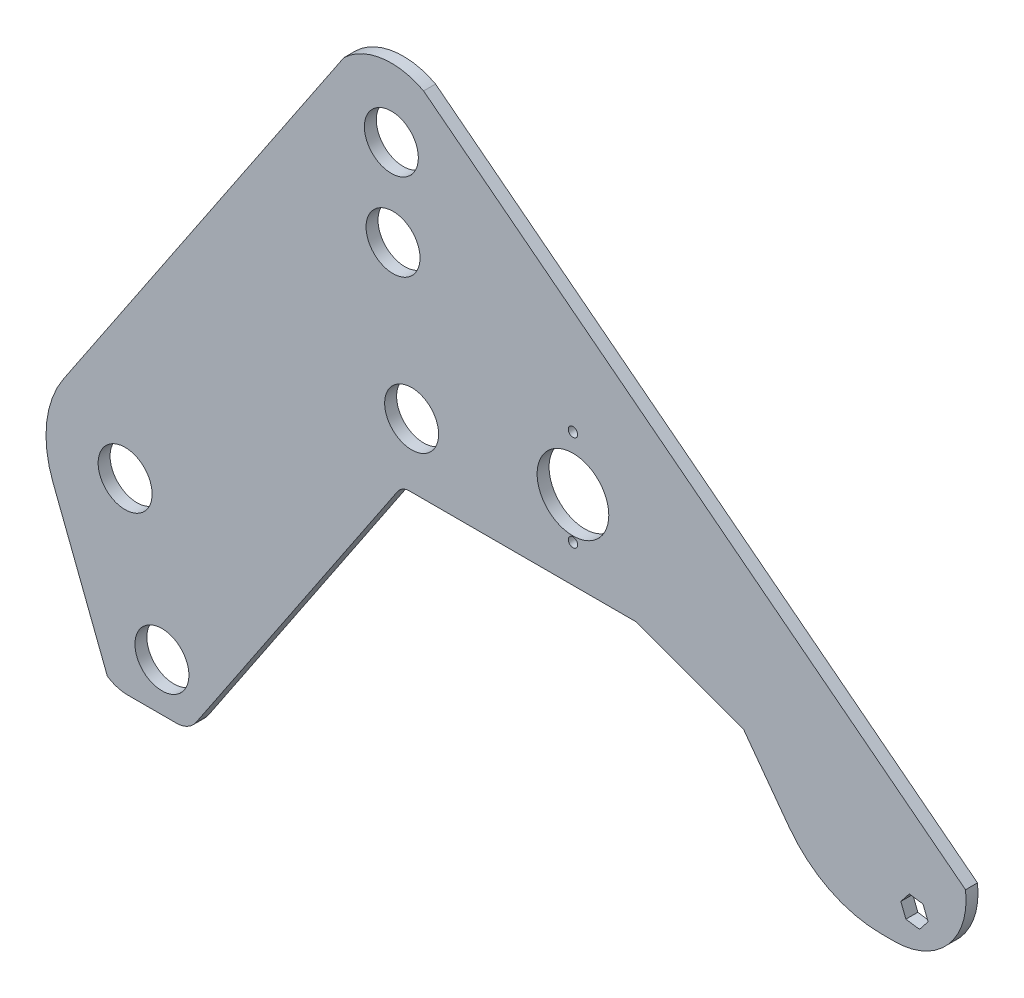
SolidWorks part; units mm, degrees
other "Markup1"
sketch "Sketch1" plane through (-441.7893, 331.8239, 6.35) normal (-0.0431, 0.0102, 0.999) x (0.9985, 0.0354, 0.0427)
sketch "Sketch2" plane through (-413.6701, 343.933, 6.35) normal (-0.0431, 0.0102, 0.999) x (0.9985, 0.0354, 0.0427)
ref_plane "Front Plane" through (0, 0, 0) normal (0, 0, 1) x (1, 0, 0)
ref_plane "Top Plane" through (0, 0, 0) normal (0, 1, 0) x (1, 0, 0)
ref_plane "Right Plane" through (0, 0, 0) normal (1, 0, 0) x (0, 0, -1)
sketch "Model" plane through (0, 0, 0) normal (0, 0, 1) x (1, 0, 0)
  line L1 (-220.9661, 94.4389) -> (-100.2963, 94.4389)
  line L3 (-334.446, -68.8406) -> (-227.2963, 91.0607)
  line L4 (-255.8627, 276.5718) -> (-404.9811, 54.0399)
  line L5 (-410.5859, 3.6373) -> (-381.6691, -71.1644)
  line L6 (-100.2963, 94.4389) -> (-43.306, 73.5035)
  line L8 (-43.306, 73.5035) -> (-19.2416, 40.7829)
  line L10 (29.8672, 15.9399) -> (36.8996, 15.9399)
  line L11 (74.721, 58.639) -> (-213.4833, 282.4355)
  line L13 (54.8115, 33.9279) -> (52.1037, 40.742)
  line L14 (52.1037, 40.742) -> (44.8487, 41.804)
  line L15 (44.8487, 41.804) -> (40.3014, 36.0519)
  line L16 (40.3014, 36.0519) -> (43.0092, 29.2379)
  line L17 (43.0092, 29.2379) -> (50.2643, 28.1759)
  line L18 (50.2643, 28.1759) -> (54.8115, 33.9279)
  line L19 (-370.9433, -74.4708) -> (-344.9963, -74.4708)
  line L20 (-862.2578, -102.4108) -> (378.8652, -102.4108) construction
  arc A2 (-213.4833, 282.4355) -> (-255.8627, 276.5718) centre (-230.622, 250.2255) ccw
  circle A3 centre (-134.0441, 114.3) radius 2.4892
  arc A6 (-220.9661, 94.4389) -> (-227.2963, 91.0607) centre (-220.9661, 86.8189) ccw
  circle A9 centre (-352.6308, -49.0708) radius 14.351
  circle A10 centre (-372.213, 24.57) radius 14.351
  circle A12 centre (-219.834, 128.3055) radius 14.351
  circle A15 centre (-134.0441, 136.2616) radius 19.05
  circle A21 centre (-134.0441, 165.1) radius 2.4892
  circle A22 centre (-229.7285, 204.5055) radius 14.351
  circle A23 centre (-230.622, 250.2255) radius 14.351
  circle A24 centre (47.5565, 34.9899) radius 6.35 construction
  arc A27 (74.721, 58.639) -> (36.8996, 15.9399) centre (36.8996, 54.0399) cw
  arc A28 (-19.2416, 40.7829) -> (29.8672, 15.9399) centre (29.8672, 76.8999) ccw
  arc A29 (-410.5859, 3.6373) -> (-404.9811, 54.0399) centre (-359.3325, 23.4508) cw
  arc A31 (-344.9963, -74.4708) -> (-334.446, -68.8406) centre (-344.9963, -61.7708) ccw
  arc A32 (-370.9433, -74.4708) -> (-381.6691, -71.1644) centre (-370.9433, -55.4208) cw
  point P19 (-404.9811, 54.0399)
  dimension "D2" = 76.2
  dimension "D3" = 38.1
  dimension "D4" = 60.96
  dimension "D5" = 7.62
  dimension "D6" = 111.135
  dimension "D1" = 127
  dimension "D7" = 12.7
  dimension "D8" = 152.4
  dimension "D11" = 127
  dimension "D12" = 27.94
  dimension "D21" = 109.4608
  dimension "D13" = 12.7
  dimension "D16" = 19.05
  dimension "D9" = 19.05
  dimension "D10" = 76.2
  dimension "D14" = 45.72
  dimension "D15" = 33.8667
  dimension "D17" = 229.5182
  dimension "D18" = 221.5793
  dimension "D19" = 41.8228
  dimension "D22" = 25.4
extrude "Boss-Extrude1" add sketch "Model" along normal blind 6.35 contours L5 L3 L1 L6 L8 L10 L11 A2 L4 A23 A22 A21 A3 A9 A10 A12 A15 region at (-212.9286, 111.7693, 0)
